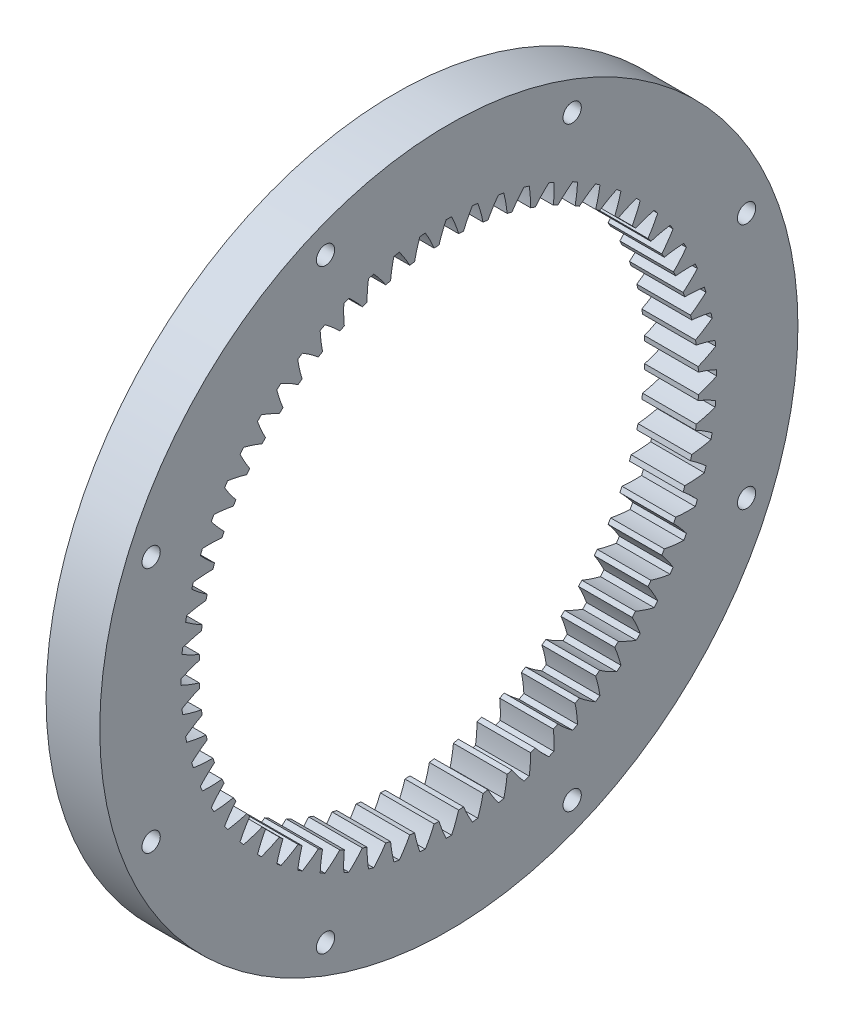
SolidWorks part; units mm, degrees
material "7075-O (SS)"
ref_plane "Plane1" through (0, 0, 0) normal (0, 0, 1) x (1, 0, 0)
ref_plane "Plane2" through (0, 0, 0) normal (0, 1, 0) x (1, 0, 0)
ref_plane "Plane3" through (0, 0, 0) normal (1, 0, 0) x (0, 0, -1)
sketch "HoldingSke" plane through (0, 0, 0) normal (0, 1, 0) x (1, 0, 0)
  line L0 (0, 0) -> (0.2922, -0.5992)
  line L1 (-15, 0) -> (100, 0) construction
  line L2 (0, 0) -> (-2.1039, 2.3779)
  line L3 (0, 0) -> (-11.863, 4.5341)
  line L4 (0, 0) -> (3.7858, 7.762)
  line L5 (0, 0) -> (-23.7986, -8.8762)
  line L6 (0, 0) -> (-10.5278, -7.1032)
  line L7 (-2.1039, 2.3779) -> (3.3635, 27.1825)
  line L8 (-76.2, 3.8779) -> (-54.61, 3.8779)
  line L9 (-71.009, 38.7566) -> (-53.1078, 45.2721)
  line L10 (-76.2, 71.12) -> (104.1128, 71.12)
  line L11 (0, 0) -> (-10, 0)
  line L12 (-76.2, 101.6) -> (-76.147, 101.6)
  line L13 (24.9733, 27.94) -> (52.9518, 28.4284)
  line L14 (24.9733, 27.94) -> (24.9743, 27.94)
  line L15 (24.9733, 27.94) -> (100.4006, 29.5858)
  circle A0 centre (0, 0) radius 55
  circle A1 centre (0, 0) radius 12.7
  circle A2 centre (0, 0) radius 12.7
  dimension "MHD" = 25.4
  dimension "Hub_dia" = 25.4
  dimension "Diameter" = 110
  dimension "Num_teeth" = 64
  dimension "Pitch" = 0.6667
  dimension "Overall_len" = 25.4
  dimension "Show_teeth" = 64
  dimension "Thickness" = 12.7
  dimension "OAL" = 25.4001
  dimension "T_dim" = 21.59
  dimension "Ap" = 20
  dimension "H" = 19.05
  dimension "Pitch_radius" = 180.3128
  dimension "Width" = 10
  dimension "Backlash" = 0.053
  dimension "Addendum_fac" = 1
  dimension "Dedendum_fac" = 1.25
  dimension "Clearance_fac" = 0.25
  dimension "Dedendum_add" = 0.001
  dimension "Module" = 1.5
sketch "BasProSke" plane through (0, 0, 0) normal (0, 1, 0) x (1, 0, 0)
  line L0 (-10, 0) -> (60, 0) construction
  line L1 (0, 46.5) -> (0, 55)
  line L2 (0, 46.5) -> (10, 46.5)
  line L3 (10, 46.5) -> (10, 55)
  line L4 (10, 55) -> (0, 55)
  dimension "Diameter" = 110
  dimension "Thickness" = 10
  dimension "Inside_diameter" = 93
revolve "Base-Revolve" add sketch "BasProSke" angle 360 about L0
sketch "TooCutSke" plane through (0, 0, 0) normal (1, 0, 0) x (0, 0, -1)
  line L3 (1.3105, 47.9821) -> (1.3105, 53.6633) construction
  line L4 (0, 0) -> (0, 59.563) construction
  line L5 (0, 0) -> (-3.3527, 68.2452) construction
  line L6 (-21.1794, 39.6032) -> (35.8053, 42.4027) construction
  circle A0 centre (0, 0) radius 48 construction
  circle A1 centre (0, 0) radius 49.876 construction
  circle A2 centre (0, 0) radius 40.5947 construction
  circle A3 centre (0, 0) radius 46.4746 construction
  arc A4 (1.8266, 46.4387) -> (0.5122, 49.8734) centre (-21.1794, 39.6032) ccw
  arc A5 (1.8266, 46.4387) -> (-1.8266, 46.4387) centre (0, 0) ccw
  arc A6 (0.5122, 49.8734) -> (-0.5122, 49.8734) centre (0, 0) ccw
  arc A7 (-0.5122, 49.8734) -> (-1.8266, 46.4387) centre (21.1794, 39.6032) ccw
  dimension "Pitch_dia" = 96
  dimension "Base_dia" = 81.1894
  dimension "Root_dia" = 99.752
  dimension "Overcut_dia" = 92.9492
  dimension "Flank_rad" = 24
  dimension "Half_ang" = 2.813
  dimension "Half_CT" = 1.3105
extrude "ToothCut" cut sketch "TooCutSke" along normal through all
fillet "Breaks" [suppressed] radius 0.15
fillet "RootFillets" [suppressed] radius 0.376
pattern_circular "TeethCuts" count 64 over 360 about axis through (-10, 0, 0) along (1, 0, 0) of "RootFillets", "Breaks", "ToothCut"
sketch "Croquis1" plane through (10, 0, 0) normal (1, 0, 0) x (0, 0, -1)
  circle A0 centre (0, 0) radius 65
  circle A1 centre (0, 0) radius 55 construction
  circle A2 centre (0, 0) radius 55
  dimension "DiametroExterior" = 130
extrude "Saliente-Extruir1" add sketch "Croquis1" against normal up to surface (10 mm away) up to face at (0, 0, 55)
hole_wizard "Taladro de margen para M31" positions "Croquis2" profile "Croquis3" hole size "M3" standard "Ansi Metric"
sketch "Croquis2" plane through (10, 0, 0) normal (1, 0, 0) x (0, 0, -1)
  line L0 (0, 0) -> (22.961, 55.4328) construction
  line L3 (0, 0) -> (-22.961, -55.4328) construction
  point P0 (22.961, 55.4328)
  point P13 (55.4328, 22.961)
  point P14 (55.4328, -22.961)
  point P15 (22.961, -55.4328)
  point P16 (-22.961, -55.4328)
  point P17 (-55.4328, -22.961)
  point P18 (-55.4328, 22.961)
  point P19 (-22.961, 55.4328)
  dimension "RadioTaladro" = 60
  dimension "D2" = 22.5
  dimension "D3" = 8
sketch "Croquis3" plane through (10, 55.4328, -22.961) normal (0, 1, 0) x (0, 0, -1)
  line L0 (0, 0) -> (0, 11.0215)
  line L1 (0, 11.0215) -> (1.7, 10)
  line L2 (1.7, 10) -> (1.7, 0)
  line L5 (1.7, 0) -> (0, 0)
  line L10 (0, 11.0215) -> (-1.7, 10) construction
  line L11 (0, -6.35) -> (0, 107.95) construction
  dimension "Diámetro de taladro" = 3.4
  dimension "Profundidad de taladro" = 10
  dimension "Ángulo de perforador" = 118
equation "' \"Module@HoldingSke\" = 6.35"
equation "' \"Num_teeth@HoldingSke\" = 24"
equation "' \"Ap@HoldingSke\" =  14.5"
equation "' \"Ap@HoldingSke\" = 14.5"
equation "' \"Width@HoldingSke\" = 12"
equation "' \"Diameter@HoldingSke\" = 8 * 25.4"
equation "' \"Show_teeth@HoldingSke\" = 100"
equation "' \"Backlash@HoldingSke\" = 0.009 * 25.4"
equation "' \"Addendum_fac@HoldingSke\" = 1.0"
equation "' \"Dedendum_fac@HoldingSke\" = 1.25"
equation "' \"Dedendum_add@HoldingSke\" = 0.00005 * 25.4"
equation "' \"Clearance_fac@HoldingSke\" = 0.25"
equation "\"Pitch@HoldingSke\" = 1 / \"Module@HoldingSke\" "
equation "\"Overcut_dia@TooCutSke\" = (\"Num_teeth@HoldingSke\" - 2 * \"Addendum_fac@HoldingSke\") / \"Pitch@HoldingSke\" - 0.002 * 25.4"
equation "\"Pitch_dia@TooCutSke\" = \"Num_teeth@HoldingSke\" / \"Pitch@HoldingSke\""
equation "\"Base_dia@TooCutSke\" = \"Num_teeth@HoldingSke\" / \"Pitch@HoldingSke\" * cos((\"Ap@HoldingSke\"  * 3.14159265 / 180)) * 0.90"
equation "\"Root_dia@TooCutSke\" = \"Num_teeth@HoldingSke\"  / \"Pitch@HoldingSke\" + 2 *  \"Dedendum_fac@HoldingSke\"/ \"Pitch@HoldingSke\" + \"Dedendum_add@HoldingSke\" * 2"
equation "\"Half_ang@TooCutSke\" = 180 / \"Num_teeth@HoldingSke\""
equation "\"Half_CT@TooCutSke\" = \"Num_teeth@HoldingSke\" / \"Pitch@HoldingSke\" * sin((3.14159265 / 2 / \"Num_teeth@HoldingSke\")) / 2 + 10 * \"Backlash@HoldingSke\" / 4"
equation "\"Flank_rad@TooCutSke\" = \"Num_teeth@HoldingSke\" / \"Pitch@HoldingSke\" / 4"
equation "\"Radius@RootFillets\"= \"Clearance_fac@HoldingSke\" / \"Pitch@HoldingSke\" + \"Dedendum_add@HoldingSke\""
equation "\"Break_rad@Breaks\" = 0.02 / \"Pitch@HoldingSke\" * 5"
equation "\"Num_teeth@TeethCuts\" = int( \"Show_teeth@HoldingSke\" ) + 1"
equation "\"Num_teeth@TeethCuts\" = ((sgn( \"Num_teeth@TeethCuts\" - \"Num_teeth@HoldingSke\" )-1)*( \"Num_teeth@TeethCuts\" - \"Num_teeth@HoldingSke\" ))/-2+ \"Num_teeth@HoldingSke\""
equation "\"Num_teeth@TeethCuts\" = ((sgn( \"Num_teeth@TeethCuts\" - 2.0)+1)*( \"Num_teeth@TeethCuts\" - 2.0))/2 +2.0"
equation "\"Angle@TeethCuts\" = 360.0 / \"Num_teeth@HoldingSke\""
equation "\"Diameter@BasProSke\" = \"Num_teeth@HoldingSke\"  / \"Pitch@HoldingSke\" + 2 *  \"Dedendum_fac@HoldingSke\"/ \"Pitch@HoldingSke\" + \"Dedendum_add@HoldingSke\" * 2 + 0.002 * 25.4"
equation "\"Diameter@BasProSke\" = ((sgn( \"Diameter@BasProSke\"  - \"Diameter@HoldingSke\" )+1)*( \"Diameter@BasProSke\"  - \"Diameter@HoldingSke\" ))/2 + \"Diameter@HoldingSke\""
equation "\"Inside_diameter@BasProSke\" =  (\"Num_teeth@HoldingSke\" - 2 * \"Addendum_fac@HoldingSke\") / \"Pitch@HoldingSke\" "
equation "\"Thickness@BasProSke\"  = \"Width@HoldingSke\""
